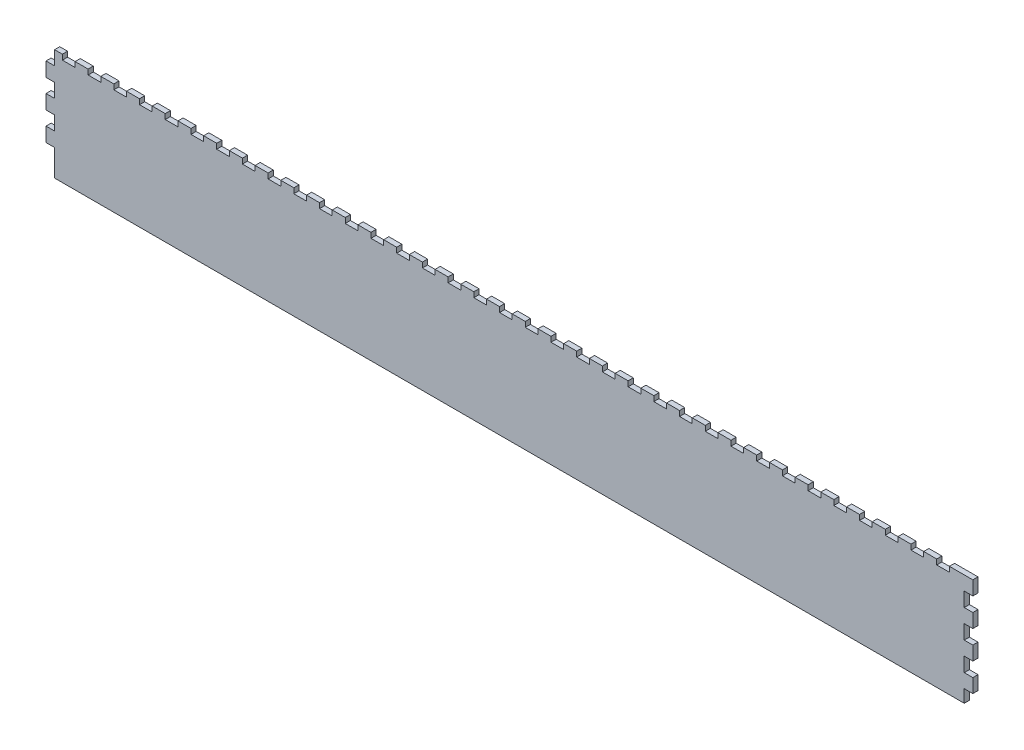
SolidWorks part; units mm, degrees
material "Perspex (TM) GS Acrylic Cast Sheet"
ref_plane "Front Plane" through (0, 0, 0) normal (0, 0, 1) x (1, 0, 0)
ref_plane "Top Plane" through (0, 0, 0) normal (0, 1, 0) x (1, 0, 0)
ref_plane "Right Plane" through (0, 0, 0) normal (1, 0, 0) x (0, 0, -1)
sketch "Sketch1" plane through (0, 0, 0) normal (0, 0, 1) x (1, 0, 0)
  line L0 (4.9997, 15.394) -> (4.9997, 0)
  line L1158 (538.3599, 64.6) -> (524.7414, 64.6)
  line L1159 (524.7414, 61.6) -> (524.7414, 64.6)
  line L1160 (524.7414, 61.6) -> (517.3729, 61.6)
  line L1161 (517.3729, 61.6) -> (517.3729, 64.6)
  line L1162 (517.3729, 64.6) -> (509.8045, 64.6)
  line L1163 (509.8045, 61.6) -> (509.8045, 64.6)
  line L1164 (509.8045, 61.6) -> (502.436, 61.6)
  line L1165 (502.436, 61.6) -> (502.436, 64.6)
  line L1166 (502.436, 64.6) -> (494.8676, 64.6)
  line L1167 (494.8676, 61.6) -> (494.8676, 64.6)
  line L1168 (494.8676, 61.6) -> (487.4991, 61.6)
  line L1169 (487.4991, 61.6) -> (487.4991, 64.6)
  line L1170 (487.4991, 64.6) -> (479.9307, 64.6)
  line L1171 (479.9307, 61.6) -> (479.9307, 64.6)
  line L1172 (479.9307, 61.6) -> (472.5622, 61.6)
  line L1173 (472.5622, 61.6) -> (472.5622, 64.6)
  line L1174 (472.5622, 64.6) -> (464.9938, 64.6)
  line L1175 (464.9938, 61.6) -> (464.9938, 64.6)
  line L1176 (464.9938, 61.6) -> (457.6253, 61.6)
  line L1177 (457.6253, 61.6) -> (457.6253, 64.6)
  line L1178 (457.6253, 64.6) -> (450.0567, 64.6)
  line L1179 (450.0567, 61.6) -> (450.0567, 64.6)
  line L1180 (450.0567, 61.6) -> (442.6886, 61.6)
  line L1181 (442.6886, 61.6) -> (442.6886, 64.6)
  line L1182 (442.6886, 64.6) -> (435.1201, 64.6)
  line L1183 (435.1201, 61.6) -> (435.1201, 64.6)
  line L1184 (435.1201, 61.6) -> (427.7516, 61.6)
  line L1185 (427.7516, 61.6) -> (427.7516, 64.6)
  line L1186 (427.7516, 64.6) -> (420.1831, 64.6)
  line L1187 (420.1831, 61.6) -> (420.1831, 64.6)
  line L1188 (420.1831, 61.6) -> (412.8147, 61.6)
  line L1189 (412.8147, 61.6) -> (412.8147, 64.6)
  line L1190 (412.8147, 64.6) -> (405.2462, 64.6)
  line L1191 (405.2462, 61.6) -> (405.2462, 64.6)
  line L1192 (405.2462, 61.6) -> (397.8777, 61.6)
  line L1193 (397.8777, 61.6) -> (397.8777, 64.6)
  line L1194 (397.8777, 64.6) -> (390.3092, 64.6)
  line L1195 (390.3092, 61.6) -> (390.3092, 64.6)
  line L1196 (390.3092, 61.6) -> (382.9407, 61.6)
  line L1197 (382.9407, 61.6) -> (382.9407, 64.6)
  line L1198 (382.9407, 64.6) -> (375.3722, 64.6)
  line L1199 (375.3722, 61.6) -> (375.3722, 64.6)
  line L1200 (375.3722, 61.6) -> (368.0038, 61.6)
  line L1201 (368.0038, 61.6) -> (368.0038, 64.6)
  line L1202 (368.0038, 64.6) -> (360.4356, 64.6)
  line L1203 (360.4356, 61.6) -> (360.4356, 64.6)
  line L1204 (360.4356, 61.6) -> (353.0672, 61.6)
  line L1205 (353.0672, 61.6) -> (353.0672, 64.6)
  line L1206 (353.0672, 64.6) -> (345.4986, 64.6)
  line L1207 (345.4986, 61.6) -> (345.4986, 64.6)
  line L1208 (345.4986, 61.6) -> (338.1302, 61.6)
  line L1209 (338.1302, 61.6) -> (338.1302, 64.6)
  line L1210 (338.1302, 64.6) -> (330.5617, 64.6)
  line L1211 (330.5617, 61.6) -> (330.5617, 64.6)
  line L1212 (330.5617, 61.6) -> (323.1932, 61.6)
  line L1213 (323.1932, 61.6) -> (323.1932, 64.6)
  line L1214 (323.1932, 64.6) -> (315.6247, 64.6)
  line L1215 (315.6247, 61.6) -> (315.6247, 64.6)
  line L1216 (315.6247, 61.6) -> (308.2563, 61.6)
  line L1217 (308.2563, 61.6) -> (308.2563, 64.6)
  line L1218 (308.2563, 64.6) -> (300.6878, 64.6)
  line L1219 (300.6878, 61.6) -> (300.6878, 64.6)
  line L1220 (300.6878, 61.6) -> (293.3193, 61.6)
  line L1221 (293.3193, 61.6) -> (293.3193, 64.6)
  line L1222 (293.3193, 64.6) -> (285.7508, 64.6)
  line L1223 (285.7508, 61.6) -> (285.7508, 64.6)
  line L1224 (285.7508, 61.6) -> (278.3823, 61.6)
  line L1225 (278.3823, 61.6) -> (278.3823, 64.6)
  line L1226 (278.3823, 64.6) -> (270.8142, 64.6)
  line L1227 (270.8142, 61.6) -> (270.8142, 64.6)
  line L1228 (270.8142, 61.6) -> (263.4457, 61.6)
  line L1229 (263.4457, 61.6) -> (263.4457, 64.6)
  line L1230 (263.4457, 64.6) -> (255.8772, 64.6)
  line L1231 (255.8772, 61.6) -> (255.8772, 64.6)
  line L1232 (255.8772, 61.6) -> (248.5088, 61.6)
  line L1233 (248.5088, 61.6) -> (248.5087, 64.6)
  line L1234 (248.5087, 64.6) -> (240.9403, 64.6)
  line L1235 (240.9403, 61.6) -> (240.9403, 64.6)
  line L1236 (240.9403, 61.6) -> (233.5718, 61.6)
  line L1237 (233.5718, 61.6) -> (233.5718, 64.6)
  line L1238 (233.5718, 64.6) -> (226.0033, 64.6)
  line L1239 (226.0033, 61.6) -> (226.0033, 64.6)
  line L1240 (226.0033, 61.6) -> (218.6348, 61.6)
  line L1241 (218.6348, 61.6) -> (218.6348, 64.6)
  line L1242 (218.6348, 64.6) -> (211.0664, 64.6)
  line L1243 (211.0664, 61.6) -> (211.0664, 64.6)
  line L1244 (211.0664, 61.6) -> (203.6979, 61.6)
  line L1245 (203.6979, 61.6) -> (203.6979, 64.6)
  line L1246 (203.6979, 64.6) -> (196.1297, 64.6)
  line L1247 (196.1297, 61.6) -> (196.1297, 64.6)
  line L1248 (196.1297, 61.6) -> (188.7613, 61.6)
  line L1249 (188.7613, 61.6) -> (188.7613, 64.6)
  line L1250 (188.7613, 64.6) -> (181.1928, 64.6)
  line L1251 (181.1928, 61.6) -> (181.1928, 64.6)
  line L1252 (181.1928, 61.6) -> (173.8243, 61.6)
  line L1253 (173.8243, 61.6) -> (173.8243, 64.6)
  line L1254 (173.8243, 64.6) -> (166.2558, 64.6)
  line L1255 (166.2558, 61.6) -> (166.2558, 64.6)
  line L1256 (166.2558, 61.6) -> (158.8873, 61.6)
  line L1257 (158.8873, 61.6) -> (158.8873, 64.6)
  line L1258 (158.8873, 64.6) -> (151.3188, 64.6)
  line L1259 (151.3188, 61.6) -> (151.3188, 64.6)
  line L1260 (151.3188, 61.6) -> (143.9504, 61.6)
  line L1261 (143.9504, 61.6) -> (143.9504, 64.6)
  line L1262 (143.9504, 64.6) -> (136.3819, 64.6)
  line L1263 (136.3819, 61.6) -> (136.3819, 64.6)
  line L1264 (136.3819, 61.6) -> (129.0134, 61.6)
  line L1265 (129.0134, 61.6) -> (129.0134, 64.6)
  line L1266 (129.0134, 64.6) -> (121.4449, 64.6)
  line L1267 (121.4449, 61.6) -> (121.4449, 64.6)
  line L1268 (121.4449, 61.6) -> (114.0764, 61.6)
  line L1269 (114.0764, 61.6) -> (114.0764, 64.6)
  line L1270 (114.0764, 64.6) -> (106.5083, 64.6)
  line L1271 (106.5083, 61.6) -> (106.5083, 64.6)
  line L1272 (106.5083, 61.6) -> (99.1398, 61.6)
  line L1273 (99.1398, 61.6) -> (99.1398, 64.6)
  line L1274 (99.1398, 64.6) -> (91.5713, 64.6)
  line L1275 (91.5713, 61.6) -> (91.5713, 64.6)
  line L1276 (91.5713, 61.6) -> (84.2029, 61.6)
  line L1277 (84.2029, 61.6) -> (84.2029, 64.6)
  line L1278 (84.2029, 64.6) -> (76.6344, 64.6)
  line L1279 (76.6344, 61.6) -> (76.6344, 64.6)
  line L1280 (76.6344, 61.6) -> (69.2659, 61.6)
  line L1281 (69.2659, 61.6) -> (69.2659, 64.6)
  line L1282 (69.2659, 64.6) -> (61.6974, 64.6)
  line L1283 (61.6974, 61.6) -> (61.6974, 64.6)
  line L1284 (61.6974, 61.6) -> (54.3289, 61.6)
  line L1285 (54.3289, 61.6) -> (54.3289, 64.6)
  line L1286 (54.3289, 64.6) -> (46.7604, 64.6)
  line L1287 (46.7604, 61.6) -> (46.7604, 64.6)
  line L1288 (46.7604, 61.6) -> (39.392, 61.6)
  line L1289 (39.392, 61.6) -> (39.392, 64.6)
  line L1290 (39.392, 64.6) -> (31.8235, 64.6)
  line L1291 (31.8235, 61.6) -> (31.8235, 64.6)
  line L1292 (31.8235, 61.6) -> (24.4554, 61.6)
  line L1293 (24.4554, 61.6) -> (24.4554, 64.6)
  line L1294 (24.4554, 64.6) -> (16.8869, 64.6)
  line L1295 (16.8869, 61.6) -> (16.8869, 64.6)
  line L1296 (16.8869, 61.6) -> (9.5184, 61.6)
  line L1297 (9.5184, 61.6) -> (9.5184, 64.6)
  line L1298 (9.5184, 64.6) -> (4.9997, 64.6)
  line L1299 (538.3599, 64.6) -> (538.3599, 56.4542)
  line L1300 (533.3598, 56.4542) -> (538.3599, 56.4542)
  line L1301 (533.3598, 56.4542) -> (533.3598, 48.1649)
  line L1302 (533.3598, 48.1649) -> (538.3599, 48.1649)
  line L1303 (538.3599, 48.1649) -> (538.3599, 40.0757)
  line L1304 (533.3598, 40.0757) -> (538.3599, 40.0757)
  line L1305 (533.3598, 40.0757) -> (533.3598, 31.7864)
  line L1306 (533.3598, 31.7864) -> (538.3599, 31.7864)
  line L1307 (538.3599, 31.7864) -> (538.3599, 23.7267)
  line L1308 (4.9997, 64.6) -> (4.9997, 56.4542)
  line L1309 (0, 56.4542) -> (4.9997, 56.4542)
  line L1310 (0, 56.4542) -> (0, 48.1649)
  line L1311 (0, 48.1649) -> (4.9997, 48.1649)
  line L1312 (4.9997, 48.1649) -> (4.9997, 40.0757)
  line L1313 (0, 40.0757) -> (4.9997, 40.0757)
  line L1314 (0, 40.0757) -> (0, 31.7864)
  line L1315 (0, 31.7864) -> (4.9997, 31.7864)
  line L1316 (4.9997, 31.7864) -> (4.9997, 23.6833)
  line L1317 (4.9997, 0) -> (533.3598, 0)
  line L1318 (533.3598, 23.7267) -> (538.3599, 23.7267)
  line L1319 (533.3598, 23.7267) -> (533.3598, 15.4209)
  line L1320 (533.3598, 15.4209) -> (538.3599, 15.4209)
  line L1321 (538.3599, 15.4209) -> (538.3599, 7.3612)
  line L1322 (533.3598, 7.3612) -> (538.3599, 7.3612)
  line L1323 (533.3598, 7.3612) -> (533.3598, 0)
  line L1324 (0, 23.6833) -> (4.9997, 23.6833)
  line L1325 (0, 23.6833) -> (0, 15.394)
  line L1326 (0, 15.394) -> (4.9997, 15.394)
extrude "Boss-Extrude1" add sketch "Sketch1" along normal blind 3
sketch "Sketch3" plane through (0, 0, 3) normal (0, 0, 1) x (1, 0, 0)
  line L0 (388.1696, 22.6554) -> (388.1696, 19.4364)
  line L1 (390.0144, 23.5966) -> (388.1696, 22.6554)
  line L2 (391.8592, 24.5377) -> (390.0144, 23.5966)
  line L3 (391.8592, 20.3776) -> (391.8592, 24.5377)
  line L4 (391.8592, 16.2174) -> (391.8592, 20.3776)
  line L5 (390.0144, 16.2174) -> (391.8592, 16.2174)
  line L6 (388.1696, 16.2174) -> (390.0144, 16.2174)
  line L7 (388.1696, 19.4364) -> (388.1696, 16.2174)
  line L8 (393.704, 27.2964) -> (393.704, 20.8345)
  line L9 (390.0144, 25.4413) -> (393.704, 27.2964)
  line L10 (386.3248, 23.5862) -> (390.0144, 25.4413)
  line L11 (386.3248, 18.9794) -> (386.3248, 23.5862)
  line L12 (386.3248, 14.3726) -> (386.3248, 18.9794)
  line L13 (390.0144, 14.3726) -> (386.3248, 14.3726)
  line L14 (393.704, 14.3726) -> (390.0144, 14.3726)
  line L15 (393.704, 20.8345) -> (393.704, 14.3726)
  line L16 (434.7504, 28.1897) -> (434.7504, 22.2036)
  line L17 (436.5952, 29.1309) -> (434.7504, 28.1897)
  line L18 (438.44, 30.072) -> (436.5952, 29.1309)
  line L19 (438.44, 23.1447) -> (438.44, 30.072)
  line L20 (438.44, 16.2174) -> (438.44, 23.1447)
  line L21 (436.5952, 16.2174) -> (438.44, 16.2174)
  line L22 (434.7504, 16.2174) -> (436.5952, 16.2174)
  line L23 (434.7504, 22.2036) -> (434.7504, 16.2174)
  line L24 (432.9056, 29.0475) -> (436.3429, 30.934)
  line L25 (432.9056, 21.7101) -> (432.9056, 29.0475)
  line L26 (432.9056, 14.3726) -> (432.9056, 21.7101)
  line L27 (436.5952, 14.3726) -> (432.9056, 14.3726)
  line L28 (440.2848, 14.3726) -> (436.5952, 14.3726)
  line L29 (440.2848, 23.5966) -> (440.2848, 14.3726)
  line L30 (146.503, 36.9712) -> (146.503, 26.5943)
  line L31 (148.3478, 36.9712) -> (146.503, 36.9712)
  line L32 (150.1926, 36.9712) -> (148.3478, 36.9712)
  line L33 (150.1926, 26.5943) -> (150.1926, 36.9712)
  line L34 (150.1926, 16.2174) -> (150.1926, 26.5943)
  line L35 (148.3478, 16.2174) -> (150.1926, 16.2174)
  line L36 (146.503, 16.2174) -> (148.3478, 16.2174)
  line L37 (146.503, 26.5943) -> (146.503, 16.2174)
  line L38 (152.0374, 38.816) -> (152.0374, 26.5943)
  line L39 (148.3478, 38.816) -> (152.0374, 38.816)
  line L40 (144.6582, 38.816) -> (148.3478, 38.816)
  line L41 (144.6582, 26.5943) -> (144.6582, 38.816)
  line L42 (144.6582, 14.3726) -> (144.6582, 26.5943)
  line L43 (148.3478, 14.3726) -> (144.6582, 14.3726)
  line L44 (152.0374, 14.3726) -> (148.3478, 14.3726)
  line L45 (152.0374, 26.5943) -> (152.0374, 14.3726)
  line L46 (186.6271, 36.9712) -> (186.6271, 26.5943)
  line L47 (188.4718, 36.9712) -> (186.6271, 36.9712)
  line L48 (190.3166, 36.9712) -> (188.4718, 36.9712)
  line L49 (190.3166, 26.5943) -> (190.3166, 36.9712)
  line L50 (190.3166, 16.2174) -> (190.3166, 26.5943)
  line L51 (188.4718, 16.2174) -> (190.3166, 16.2174)
  line L52 (186.6271, 16.2174) -> (188.4718, 16.2174)
  line L53 (186.6271, 26.5943) -> (186.6271, 16.2174)
  line L54 (192.1614, 38.816) -> (192.1614, 26.5943)
  line L55 (188.4718, 38.816) -> (192.1614, 38.816)
  line L56 (184.7823, 38.816) -> (188.4718, 38.816)
  line L57 (184.7823, 26.5943) -> (184.7823, 38.816)
  line L58 (184.7823, 14.3726) -> (184.7823, 26.5943)
  line L59 (188.4718, 14.3726) -> (184.7823, 14.3726)
  line L60 (192.1614, 14.3726) -> (188.4718, 14.3726)
  line L61 (192.1614, 26.5943) -> (192.1614, 14.3726)
  line L62 (393.704, 38.816) -> (393.704, 35.1213)
  line L63 (390.0144, 38.816) -> (393.704, 38.816)
  line L64 (386.3248, 38.816) -> (390.0144, 38.816)
  line L65 (386.3248, 36.9764) -> (386.3248, 38.816)
  line L66 (393.704, 31.4266) -> (390.0144, 33.2817)
  line L67 (393.704, 35.1213) -> (393.704, 31.4266)
  line L68 (307.6212, 47.3012) -> (307.6214, 47.3012)
  line L69 (305.9931, 14.3726) -> (306.1502, 32.1059)
  line L70 (308.802, 14.3726) -> (305.9931, 14.3726)
  line L71 (311.611, 14.3726) -> (308.802, 14.3726)
  line L72 (311.611, 12.5279) -> (311.611, 14.3726)
  line L73 (311.611, 10.683) -> (311.611, 12.5279)
  line L74 (304.2319, 10.683) -> (311.611, 10.683)
  line L75 (296.8527, 10.683) -> (304.2319, 10.683)
  line L76 (296.8527, 12.5279) -> (296.8527, 10.683)
  line L77 (296.8527, 14.3726) -> (296.8527, 12.5279)
  line L78 (299.6653, 14.3726) -> (296.8527, 14.3726)
  line L79 (302.478, 14.3726) -> (299.6653, 14.3726)
  line L80 (302.3172, 32.1058) -> (302.478, 14.3726)
  line L81 (300.5424, 16.2174) -> (300.5455, 30.3992)
  line L82 (297.7752, 16.2174) -> (300.5424, 16.2174)
  line L83 (295.0081, 16.2174) -> (297.7752, 16.2174)
  line L84 (295.0081, 12.5279) -> (295.0081, 16.2174)
  line L85 (295.0081, 8.8383) -> (295.0081, 12.5279)
  line L86 (304.232, 8.8383) -> (295.0081, 8.8383)
  line L87 (313.4559, 8.8383) -> (304.232, 8.8383)
  line L88 (313.4559, 12.5279) -> (313.4559, 8.8383)
  line L89 (313.4559, 16.2174) -> (313.4559, 12.5279)
  line L90 (310.6887, 16.2174) -> (313.4559, 16.2174)
  line L91 (307.9215, 16.2174) -> (310.6887, 16.2174)
  line L92 (307.9215, 29.9837) -> (307.9215, 16.2174)
  line L93 (434.8264, 41.7178) -> (436.4182, 40.9587)
  line L94 (434.5024, 46.0388) -> (434.8264, 41.7178)
  line L95 (440.2848, 36.9084) -> (436.5956, 38.8999)
  line L96 (440.2848, 40.3292) -> (440.2848, 36.9084)
  line L97 (443.8891, 10.683) -> (444.0767, 29.938)
  line L98 (436.5526, 10.683) -> (443.8891, 10.683)
  line L99 (429.2161, 10.683) -> (436.5526, 10.683)
  line L100 (429.2161, 21.1916) -> (429.2161, 10.683)
  line L101 (429.2161, 31.7001) -> (429.2161, 21.1916)
  line L102 (432.2682, 33.2052) -> (429.2161, 31.7001)
  line L103 (429.4466, 38.1242) -> (432.0696, 36.7311)
  line L104 (429.108, 43.1974) -> (429.4466, 38.1242)
  line L105 (427.3713, 37.155) -> (427.4169, 41.7904)
  line L106 (429.5604, 36.0915) -> (427.3713, 37.155)
  line L107 (431.7495, 35.0279) -> (429.5604, 36.0915)
  line L108 (429.5604, 33.9153) -> (431.7495, 35.0279)
  line L109 (427.3713, 32.8028) -> (429.5604, 33.9153)
  line L110 (427.3713, 20.8205) -> (427.3713, 32.8028)
  line L111 (427.3713, 8.8383) -> (427.3713, 20.8205)
  line L112 (436.5952, 8.8383) -> (427.3713, 8.8383)
  line L113 (445.8191, 8.8383) -> (436.5952, 8.8383)
  line L115 (445.8191, 26.5247) -> (445.8191, 8.8383)
  line L116 (209.3814, 48.2705) -> (209.3813, 48.2705)
  line L117 (213.607, 33.0511) -> (213.8934, 39.969)
  line L118 (211.6626, 38.816) -> (213.607, 33.0511)
  line L119 (226.29, 8.8383) -> (226.3356, 28.0932)
  line L120 (229.9795, 8.8383) -> (226.29, 8.8383)
  line L121 (233.6691, 8.8383) -> (229.9795, 8.8383)
  line L122 (233.6691, 20.1376) -> (233.6691, 8.8383)
  line L123 (233.6691, 31.4369) -> (233.6691, 20.1376)
  line L124 (235.5139, 31.4369) -> (233.6691, 31.4369)
  line L125 (237.3587, 31.4369) -> (235.5139, 31.4369)
  line L126 (237.3587, 20.1376) -> (237.3587, 31.4369)
  line L127 (237.3587, 8.8383) -> (237.3587, 20.1376)
  line L128 (241.0482, 8.8383) -> (237.3587, 8.8383)
  line L129 (244.7378, 8.8383) -> (241.0482, 8.8383)
  line L130 (244.735, 26.2484) -> (244.7378, 8.8383)
  line L131 (242.814, 10.683) -> (243.0138, 29.7074)
  line L132 (241.0087, 10.683) -> (242.814, 10.683)
  line L133 (239.2034, 10.683) -> (241.0087, 10.683)
  line L134 (239.2034, 21.9824) -> (239.2034, 10.683)
  line L135 (239.2034, 33.2817) -> (239.2034, 21.9824)
  line L136 (235.5138, 33.2817) -> (239.2034, 33.2817)
  line L137 (231.8242, 33.2817) -> (235.5138, 33.2817)
  line L138 (231.8242, 21.9824) -> (231.8242, 33.2817)
  line L139 (231.8242, 10.683) -> (231.8242, 21.9824)
  line L140 (230.0246, 10.683) -> (231.8242, 10.683)
  line L141 (228.225, 10.683) -> (230.0246, 10.683)
  line L142 (228.0101, 30.3992) -> (228.225, 10.683)
  line L143 (115.6029, 25.9025) -> (115.6485, 37.5477)
  line L144 (119.2925, 25.9025) -> (115.6029, 25.9025)
  line L145 (122.982, 25.9025) -> (119.2925, 25.9025)
  line L146 (122.982, 31.4369) -> (122.982, 25.9025)
  line L147 (122.982, 36.9712) -> (122.982, 31.4369)
  line L148 (124.8268, 36.9712) -> (122.982, 36.9712)
  line L149 (126.6716, 36.9712) -> (124.8268, 36.9712)
  line L150 (126.6716, 26.5943) -> (126.6716, 36.9712)
  line L151 (126.6716, 16.2174) -> (126.6716, 26.5943)
  line L152 (124.8268, 16.2174) -> (126.6716, 16.2174)
  line L153 (122.982, 16.2174) -> (124.8268, 16.2174)
  line L154 (122.982, 18.9846) -> (122.982, 16.2174)
  line L155 (122.982, 21.7517) -> (122.982, 18.9846)
  line L156 (119.2925, 21.7517) -> (122.982, 21.7517)
  line L157 (115.6029, 21.7517) -> (119.2925, 21.7517)
  line L158 (115.6029, 15.295) -> (115.6029, 21.7517)
  line L159 (115.6029, 8.8383) -> (115.6029, 15.295)
  line L160 (124.8268, 8.8383) -> (115.6029, 8.8383)
  line L161 (134.0507, 8.8383) -> (124.8268, 8.8383)
  line L162 (134.0507, 26.0635) -> (134.0507, 8.8383)
  line L163 (132.1262, 10.683) -> (132.3074, 29.4768)
  line L164 (124.787, 10.683) -> (132.1262, 10.683)
  line L165 (117.4477, 10.683) -> (124.787, 10.683)
  line L166 (117.4477, 15.295) -> (117.4477, 10.683)
  line L167 (117.4477, 19.907) -> (117.4477, 15.295)
  line L168 (119.2925, 19.907) -> (117.4477, 19.907)
  line L169 (121.1373, 19.907) -> (119.2925, 19.907)
  line L170 (121.1373, 17.1398) -> (121.1373, 19.907)
  line L171 (121.1373, 14.3726) -> (121.1373, 17.1398)
  line L172 (124.8268, 14.3726) -> (121.1373, 14.3726)
  line L173 (128.5164, 14.3726) -> (124.8268, 14.3726)
  line L174 (128.5164, 26.5943) -> (128.5164, 14.3726)
  line L175 (128.5164, 38.816) -> (128.5164, 26.5943)
  line L176 (124.8268, 38.816) -> (128.5164, 38.816)
  line L177 (121.1373, 38.816) -> (124.8268, 38.816)
  line L178 (121.1373, 33.2817) -> (121.1373, 38.816)
  line L179 (121.1373, 27.7473) -> (121.1373, 33.2817)
  line L180 (119.3512, 27.7473) -> (121.1373, 27.7473)
  line L181 (117.565, 27.7473) -> (119.3512, 27.7473)
  line L182 (117.3014, 39.6231) -> (117.565, 27.7473)
  line L183 (173.8694, 51.0505) -> (173.8695, 51.0505)
  line L184 (172.2496, 10.683) -> (172.4314, 31.5522)
  line L185 (170.445, 10.683) -> (172.2496, 10.683)
  line L186 (168.6403, 10.683) -> (170.445, 10.683)
  line L187 (168.6403, 24.7495) -> (168.6403, 10.683)
  line L188 (168.6403, 38.816) -> (168.6403, 24.7495)
  line L189 (165.9388, 38.816) -> (168.6403, 38.816)
  line L190 (163.2372, 38.816) -> (165.9388, 38.816)
  line L191 (162.9119, 44.0045) -> (163.2372, 38.816)
  line L192 (161.2613, 36.9712) -> (161.2644, 40.3149)
  line L193 (164.0285, 36.9712) -> (161.2613, 36.9712)
  line L194 (166.7956, 36.9712) -> (164.0285, 36.9712)
  line L195 (166.7956, 22.9047) -> (166.7956, 36.9712)
  line L196 (166.7956, 8.8383) -> (166.7956, 22.9047)
  line L197 (170.4852, 8.8383) -> (166.7956, 8.8383)
  line L198 (174.1748, 8.8383) -> (170.4852, 8.8383)
  line L199 (174.1748, 28.1389) -> (174.1748, 8.8383)
  line L200 (249.3497, 31.4369) -> (249.3953, 40.5455)
  line L201 (253.0393, 31.4369) -> (249.3497, 31.4369)
  line L202 (256.7288, 31.4369) -> (253.0393, 31.4369)
  line L203 (256.7288, 34.204) -> (256.7288, 31.4369)
  line L204 (256.7288, 36.9712) -> (256.7288, 34.204)
  line L205 (258.5736, 36.9712) -> (256.7288, 36.9712)
  line L206 (260.4184, 36.9712) -> (258.5736, 36.9712)
  line L207 (260.4184, 26.5943) -> (260.4184, 36.9712)
  line L208 (260.4184, 16.2174) -> (260.4184, 26.5943)
  line L209 (258.5736, 16.2174) -> (260.4184, 16.2174)
  line L210 (256.7288, 16.2174) -> (258.5736, 16.2174)
  line L211 (256.7288, 18.9846) -> (256.7288, 16.2174)
  line L212 (256.7288, 21.7517) -> (256.7288, 18.9846)
  line L213 (253.0393, 21.7517) -> (256.7288, 21.7517)
  line L214 (249.3497, 21.7517) -> (253.0393, 21.7517)
  line L215 (249.3497, 15.295) -> (249.3497, 21.7517)
  line L216 (249.3497, 8.8383) -> (249.3497, 15.295)
  line L217 (258.5736, 8.8383) -> (249.3497, 8.8383)
  line L218 (267.7975, 8.8383) -> (258.5736, 8.8383)
  line L219 (267.7975, 26.2941) -> (267.7975, 8.8383)
  line L220 (265.8667, 10.683) -> (266.0553, 29.7074)
  line L221 (258.5306, 10.683) -> (265.8667, 10.683)
  line L222 (251.1945, 10.683) -> (258.5306, 10.683)
  line L223 (251.1945, 15.295) -> (251.1945, 10.683)
  line L224 (251.1945, 19.907) -> (251.1945, 15.295)
  line L225 (253.0393, 19.907) -> (251.1945, 19.907)
  line L226 (254.884, 19.907) -> (253.0393, 19.907)
  line L227 (254.884, 17.1398) -> (254.884, 19.907)
  line L228 (254.884, 14.3726) -> (254.884, 17.1398)
  line L229 (258.5736, 14.3726) -> (254.884, 14.3726)
  line L230 (262.2632, 14.3726) -> (258.5736, 14.3726)
  line L231 (262.2632, 26.5943) -> (262.2632, 14.3726)
  line L232 (262.2632, 38.816) -> (262.2632, 26.5943)
  line L233 (258.5736, 38.816) -> (262.2632, 38.816)
  line L234 (254.884, 38.816) -> (258.5736, 38.816)
  line L235 (254.884, 36.0488) -> (254.884, 38.816)
  line L236 (254.884, 33.2817) -> (254.884, 36.0488)
  line L237 (253.1053, 33.2817) -> (254.884, 33.2817)
  line L238 (251.3265, 33.2817) -> (253.1053, 33.2817)
  line L239 (251.0415, 42.6209) -> (251.3265, 33.2817)
  line L240 (352.3522, 51.0505) -> (352.3523, 51.0505)
  line L241 (350.7324, 10.683) -> (350.9142, 31.5522)
  line L242 (348.9277, 10.683) -> (350.7324, 10.683)
  line L243 (347.1231, 10.683) -> (348.9277, 10.683)
  line L244 (347.1231, 24.7495) -> (347.1231, 10.683)
  line L245 (347.1231, 38.816) -> (347.1231, 24.7495)
  line L246 (344.4215, 38.816) -> (347.1231, 38.816)
  line L247 (341.72, 38.816) -> (344.4215, 38.816)
  line L248 (341.3947, 44.0045) -> (341.72, 38.816)
  line L249 (339.7441, 36.9712) -> (339.7472, 40.3149)
  line L250 (342.5112, 36.9712) -> (339.7441, 36.9712)
  line L251 (345.2784, 36.9712) -> (342.5112, 36.9712)
  line L252 (345.2784, 22.9047) -> (345.2784, 36.9712)
  line L253 (345.2784, 8.8383) -> (345.2784, 22.9047)
  line L254 (348.968, 8.8383) -> (345.2784, 8.8383)
  line L255 (352.6576, 8.8383) -> (348.968, 8.8383)
  line L256 (352.6576, 28.1389) -> (352.6576, 8.8383)
  line L257 (397.3133, 10.683) -> (397.4951, 31.5522)
  line L258 (389.9743, 10.683) -> (397.3133, 10.683)
  line L259 (382.6353, 10.683) -> (389.9743, 10.683)
  line L260 (382.6353, 18.4244) -> (382.6353, 10.683)
  line L261 (382.6353, 26.1657) -> (382.6353, 18.4244)
  line L262 (385.6874, 27.6708) -> (382.6353, 26.1657)
  line L263 (382.8659, 32.5898) -> (385.4889, 31.1967)
  line L264 (382.5801, 40.208) -> (382.8659, 32.5898)
  line L265 (380.7905, 31.6207) -> (380.8361, 38.7926)
  line L266 (382.9665, 30.5635) -> (380.7905, 31.6207)
  line L267 (385.1425, 29.5063) -> (382.9665, 30.5635)
  line L268 (383.3124, 28.3986) -> (385.1425, 29.5063)
  line L269 (380.7905, 8.8383) -> (380.7905, 18.0622)
  line L270 (390.0144, 8.8383) -> (380.7905, 8.8383)
  line L271 (399.2383, 8.8383) -> (390.0144, 8.8383)
  line L272 (399.2383, 28.1389) -> (399.2383, 8.8383)
  line L273 (272.4095, 36.9712) -> (272.4551, 43.5433)
  line L274 (277.9438, 36.9712) -> (272.4095, 36.9712)
  line L275 (283.4782, 36.9712) -> (277.9438, 36.9712)
  line L276 (283.4782, 35.1264) -> (283.4782, 36.9712)
  line L277 (283.4782, 33.2817) -> (283.4782, 35.1264)
  line L278 (277.9438, 33.2817) -> (283.4782, 33.2817)
  line L279 (272.4095, 33.2817) -> (277.9438, 33.2817)
  line L280 (272.4095, 29.5921) -> (272.4095, 33.2817)
  line L281 (272.4095, 25.9025) -> (272.4095, 29.5921)
  line L282 (277.9438, 25.9025) -> (272.4095, 25.9025)
  line L283 (283.4782, 25.9025) -> (277.9438, 25.9025)
  line L284 (283.4782, 21.06) -> (283.4782, 25.9025)
  line L285 (283.4782, 16.2174) -> (283.4782, 21.06)
  line L286 (281.6334, 16.2174) -> (283.4782, 16.2174)
  line L287 (279.7886, 16.2174) -> (281.6334, 16.2174)
  line L288 (279.7886, 18.9846) -> (279.7886, 16.2174)
  line L289 (279.7886, 21.7517) -> (279.7886, 18.9846)
  line L290 (276.099, 21.7517) -> (279.7886, 21.7517)
  line L291 (272.4095, 21.7517) -> (276.099, 21.7517)
  line L292 (272.4095, 15.295) -> (272.4095, 21.7517)
  line L293 (272.4095, 8.8383) -> (272.4095, 15.295)
  line L294 (281.6334, 8.8383) -> (272.4095, 8.8383)
  line L295 (290.8573, 8.8383) -> (281.6334, 8.8383)
  line L296 (290.8573, 26.9859) -> (290.8573, 8.8383)
  line L297 (288.9288, 10.683) -> (289.1147, 30.3992)
  line L298 (281.5915, 10.683) -> (288.9288, 10.683)
  line L299 (274.2543, 10.683) -> (281.5915, 10.683)
  line L300 (274.2543, 15.295) -> (274.2543, 10.683)
  line L301 (274.2543, 19.907) -> (274.2543, 15.295)
  line L302 (276.099, 19.907) -> (274.2543, 19.907)
  line L303 (277.9438, 19.907) -> (276.099, 19.907)
  line L304 (277.9438, 17.1398) -> (277.9438, 19.907)
  line L305 (277.9438, 14.3726) -> (277.9438, 17.1398)
  line L306 (281.6334, 14.3726) -> (277.9438, 14.3726)
  line L307 (285.323, 14.3726) -> (281.6334, 14.3726)
  line L308 (285.323, 21.06) -> (285.323, 14.3726)
  line L309 (285.323, 27.7473) -> (285.323, 21.06)
  line L310 (279.7886, 27.7473) -> (285.323, 27.7473)
  line L311 (274.2543, 27.7473) -> (279.7886, 27.7473)
  line L312 (274.2543, 29.5921) -> (274.2543, 27.7473)
  line L313 (274.2543, 31.4369) -> (274.2543, 29.5921)
  line L314 (279.7886, 31.4369) -> (274.2543, 31.4369)
  line L315 (285.323, 31.4369) -> (279.7886, 31.4369)
  line L316 (285.323, 35.1264) -> (285.323, 31.4369)
  line L317 (285.323, 38.816) -> (285.323, 35.1264)
  line L318 (279.8603, 38.816) -> (285.323, 38.816)
  line L319 (274.3977, 38.816) -> (279.8603, 38.816)
  line L320 (274.0865, 45.6186) -> (274.3977, 38.816)
  line L321 (357.2695, 36.9712) -> (357.3151, 43.5433)
  line L322 (362.8039, 36.9712) -> (357.2695, 36.9712)
  line L323 (368.3382, 36.9712) -> (362.8039, 36.9712)
  line L324 (368.3382, 35.1264) -> (368.3382, 36.9712)
  line L325 (368.3382, 33.2817) -> (368.3382, 35.1264)
  line L326 (362.8039, 33.2817) -> (368.3382, 33.2817)
  line L327 (357.2695, 33.2817) -> (362.8039, 33.2817)
  line L328 (357.2695, 29.5921) -> (357.2695, 33.2817)
  line L329 (357.2695, 25.9025) -> (357.2695, 29.5921)
  line L330 (362.8039, 25.9025) -> (357.2695, 25.9025)
  line L331 (368.3382, 25.9025) -> (362.8039, 25.9025)
  line L332 (368.3382, 21.06) -> (368.3382, 25.9025)
  line L333 (368.3382, 16.2174) -> (368.3382, 21.06)
  line L334 (366.4934, 16.2174) -> (368.3382, 16.2174)
  line L335 (364.6486, 16.2174) -> (366.4934, 16.2174)
  line L336 (364.6486, 18.9846) -> (364.6486, 16.2174)
  line L337 (364.6486, 21.7517) -> (364.6486, 18.9846)
  line L338 (360.9591, 21.7517) -> (364.6486, 21.7517)
  line L339 (357.2695, 21.7517) -> (360.9591, 21.7517)
  line L340 (357.2695, 15.295) -> (357.2695, 21.7517)
  line L341 (357.2695, 8.8383) -> (357.2695, 15.295)
  line L342 (366.4934, 8.8383) -> (357.2695, 8.8383)
  line L343 (375.7173, 8.8383) -> (366.4934, 8.8383)
  line L344 (375.7173, 26.9859) -> (375.7173, 8.8383)
  line L345 (373.7888, 10.683) -> (373.9747, 30.3992)
  line L346 (366.4515, 10.683) -> (373.7888, 10.683)
  line L347 (359.1143, 10.683) -> (366.4515, 10.683)
  line L348 (359.1143, 15.295) -> (359.1143, 10.683)
  line L349 (359.1143, 19.907) -> (359.1143, 15.295)
  line L350 (360.9591, 19.907) -> (359.1143, 19.907)
  line L351 (362.8039, 19.907) -> (360.9591, 19.907)
  line L352 (362.8039, 17.1398) -> (362.8039, 19.907)
  line L353 (362.8039, 14.3726) -> (362.8039, 17.1398)
  line L354 (366.4934, 14.3726) -> (362.8039, 14.3726)
  line L355 (370.183, 14.3726) -> (366.4934, 14.3726)
  line L356 (370.183, 21.06) -> (370.183, 14.3726)
  line L357 (370.183, 27.7473) -> (370.183, 21.06)
  line L358 (364.6486, 27.7473) -> (370.183, 27.7473)
  line L359 (359.1143, 27.7473) -> (364.6486, 27.7473)
  line L360 (359.1143, 29.5921) -> (359.1143, 27.7473)
  line L361 (359.1143, 31.4369) -> (359.1143, 29.5921)
  line L362 (364.6486, 31.4369) -> (359.1143, 31.4369)
  line L363 (370.183, 31.4369) -> (364.6486, 31.4369)
  line L364 (370.183, 35.1264) -> (370.183, 31.4369)
  line L365 (370.183, 38.816) -> (370.183, 35.1264)
  line L366 (364.7204, 38.816) -> (370.183, 38.816)
  line L367 (359.2577, 38.816) -> (364.7204, 38.816)
  line L368 (358.9465, 45.6186) -> (359.2577, 38.816)
  line L369 (403.8503, 36.9712) -> (403.8959, 43.5433)
  line L370 (409.3846, 36.9712) -> (403.8503, 36.9712)
  line L371 (414.919, 36.9712) -> (409.3846, 36.9712)
  line L372 (414.919, 35.1264) -> (414.919, 36.9712)
  line L373 (414.919, 33.2817) -> (414.919, 35.1264)
  line L374 (409.3846, 33.2817) -> (414.919, 33.2817)
  line L375 (403.8503, 33.2817) -> (409.3846, 33.2817)
  line L376 (403.8503, 29.5921) -> (403.8503, 33.2817)
  line L377 (403.8503, 25.9025) -> (403.8503, 29.5921)
  line L378 (409.3846, 25.9025) -> (403.8503, 25.9025)
  line L379 (414.919, 25.9025) -> (409.3846, 25.9025)
  line L380 (414.919, 21.06) -> (414.919, 25.9025)
  line L381 (414.919, 16.2174) -> (414.919, 21.06)
  line L382 (413.0742, 16.2174) -> (414.919, 16.2174)
  line L383 (411.2294, 16.2174) -> (413.0742, 16.2174)
  line L384 (411.2294, 18.9846) -> (411.2294, 16.2174)
  line L385 (411.2294, 21.7517) -> (411.2294, 18.9846)
  line L386 (407.5398, 21.7517) -> (411.2294, 21.7517)
  line L387 (403.8503, 21.7517) -> (407.5398, 21.7517)
  line L388 (403.8503, 15.295) -> (403.8503, 21.7517)
  line L389 (403.8503, 8.8383) -> (403.8503, 15.295)
  line L390 (413.0742, 8.8383) -> (403.8503, 8.8383)
  line L391 (422.2981, 8.8383) -> (413.0742, 8.8383)
  line L393 (422.2981, 26.9859) -> (422.2981, 8.8383)
  line L394 (420.3695, 10.683) -> (420.5554, 30.3992)
  line L395 (413.0323, 10.683) -> (420.3695, 10.683)
  line L396 (405.6951, 10.683) -> (413.0323, 10.683)
  line L397 (405.6951, 15.295) -> (405.6951, 10.683)
  line L398 (405.6951, 19.907) -> (405.6951, 15.295)
  line L399 (407.5398, 19.907) -> (405.6951, 19.907)
  line L400 (409.3846, 19.907) -> (407.5398, 19.907)
  line L401 (409.3846, 17.1398) -> (409.3846, 19.907)
  line L402 (409.3846, 14.3726) -> (409.3846, 17.1398)
  line L403 (413.0742, 14.3726) -> (409.3846, 14.3726)
  line L404 (416.7638, 14.3726) -> (413.0742, 14.3726)
  line L405 (416.7638, 21.06) -> (416.7638, 14.3726)
  line L406 (416.7638, 27.7473) -> (416.7638, 21.06)
  line L407 (411.2294, 27.7473) -> (416.7638, 27.7473)
  line L408 (405.6951, 27.7473) -> (411.2294, 27.7473)
  line L409 (405.6951, 29.5921) -> (405.6951, 27.7473)
  line L410 (405.6951, 31.4369) -> (405.6951, 29.5921)
  line L411 (411.2294, 31.4369) -> (405.6951, 31.4369)
  line L412 (416.7638, 31.4369) -> (411.2294, 31.4369)
  line L413 (416.7638, 35.1264) -> (416.7638, 31.4369)
  line L414 (416.7638, 38.816) -> (416.7638, 35.1264)
  line L415 (411.3011, 38.816) -> (416.7638, 38.816)
  line L416 (405.8385, 38.816) -> (411.3011, 38.816)
  line L417 (405.5273, 45.6186) -> (405.8385, 38.816)
  line L418 (157.2664, 52.4341) -> (157.2665, 52.4341)
  line L419 (155.6485, 10.683) -> (155.828, 32.244)
  line L420 (148.3516, 10.683) -> (155.6485, 10.683)
  line L421 (141.0546, 10.683) -> (148.3516, 10.683)
  line L422 (140.866, 29.7074) -> (141.0546, 10.683)
  line L423 (139.1239, 8.8383) -> (139.127, 26.7096)
  line L424 (148.3478, 8.8383) -> (139.1239, 8.8383)
  line L425 (157.5717, 8.8383) -> (148.3478, 8.8383)
  line L426 (157.5717, 28.8307) -> (157.5717, 8.8383)
  line L427 (197.3904, 52.4341) -> (197.3905, 52.4341)
  line L428 (195.7726, 10.683) -> (195.9521, 32.244)
  line L429 (188.4756, 10.683) -> (195.7726, 10.683)
  line L430 (181.1786, 10.683) -> (188.4756, 10.683)
  line L431 (180.9901, 29.7074) -> (181.1786, 10.683)
  line L432 (179.2479, 8.8383) -> (179.251, 26.7096)
  line L433 (188.4718, 8.8383) -> (179.2479, 8.8383)
  line L434 (197.6958, 8.8383) -> (188.4718, 8.8383)
  line L435 (197.6958, 28.8307) -> (197.6958, 8.8383)
  line L436 (238.9031, 52.3743) -> (238.9032, 52.3743)
  line L437 (237.2189, 38.816) -> (237.4814, 46.9413)
  line L438 (235.5032, 38.816) -> (237.2189, 38.816)
  line L439 (233.7876, 38.816) -> (235.5032, 38.816)
  line L440 (233.4589, 43.8858) -> (233.7876, 38.816)
  line L441 (231.8242, 36.9712) -> (231.8274, 40.0843)
  line L442 (235.5138, 36.9712) -> (231.8242, 36.9712)
  line L443 (239.2034, 36.9712) -> (235.5138, 36.9712)
  line L444 (239.2034, 42.8972) -> (239.2034, 36.9712)
  line L445 (220.9063, 52.9282) -> (220.9065, 52.9282)
  line L446 (219.3002, 10.683) -> (219.4918, 32.244)
  line L447 (217.333, 10.683) -> (219.3002, 10.683)
  line L448 (215.3659, 10.683) -> (217.333, 10.683)
  line L449 (211.9498, 20.6957) -> (215.3659, 10.683)
  line L450 (208.5337, 30.7084) -> (211.9498, 20.6957)
  line L451 (208.4094, 20.6957) -> (208.5337, 30.7084)
  line L452 (208.2851, 10.683) -> (208.4094, 20.6957)
  line L453 (206.4912, 10.683) -> (208.2851, 10.683)
  line L454 (204.6973, 10.683) -> (206.4912, 10.683)
  line L455 (204.492, 30.3992) -> (204.6973, 10.683)
  line L456 (202.7689, 8.8383) -> (202.772, 27.632)
  line L457 (206.4585, 8.8383) -> (202.7689, 8.8383)
  line L458 (210.148, 8.8383) -> (206.4585, 8.8383)
  line L459 (210.1795, 14.4879) -> (210.148, 8.8383)
  line L460 (210.2109, 20.1376) -> (210.1795, 14.4879)
  line L461 (212.1395, 14.6032) -> (210.2109, 20.1376)
  line L462 (214.0682, 9.0689) -> (212.1395, 14.6032)
  line L463 (217.6425, 8.9342) -> (214.0682, 9.0689)
  line L464 (221.2167, 8.7995) -> (217.6425, 8.9342)
  line L465 (221.2167, 29.0419) -> (221.2167, 8.7995)
  line L466 (110.6808, 53.3894) -> (110.6806, 53.3894)
  line L467 (109.0112, 38.816) -> (109.2853, 46.541)
  line L468 (103.5444, 38.816) -> (109.0112, 38.816)
  line L469 (98.0776, 38.816) -> (103.5444, 38.816)
  line L470 (98.0776, 35.1264) -> (98.0776, 38.816)
  line L471 (98.0776, 31.4369) -> (98.0776, 35.1264)
  line L472 (103.612, 31.4369) -> (98.0776, 31.4369)
  line L473 (109.1463, 31.4369) -> (103.612, 31.4369)
  line L474 (109.1463, 21.06) -> (109.1463, 31.4369)
  line L475 (109.1463, 10.683) -> (109.1463, 21.06)
  line L476 (107.3016, 10.683) -> (109.1463, 10.683)
  line L477 (105.4568, 10.683) -> (107.3016, 10.683)
  line L478 (105.4568, 19.2152) -> (105.4568, 10.683)
  line L479 (105.4568, 27.7473) -> (105.4568, 19.2152)
  line L480 (101.7672, 27.7473) -> (105.4568, 27.7473)
  line L481 (98.0776, 27.7473) -> (101.7672, 27.7473)
  line L482 (98.0776, 19.2152) -> (98.0776, 27.7473)
  line L483 (98.0776, 10.683) -> (98.0776, 19.2152)
  line L484 (96.2762, 10.683) -> (98.0776, 10.683)
  line L485 (94.4749, 10.683) -> (96.2762, 10.683)
  line L486 (94.2854, 29.4768) -> (94.4749, 10.683)
  line L487 (92.5431, 8.8383) -> (92.5465, 26.479)
  line L488 (96.2327, 8.8383) -> (92.5431, 8.8383)
  line L489 (99.9222, 8.8383) -> (96.2327, 8.8383)
  line L490 (99.9222, 17.3704) -> (99.9222, 8.8383)
  line L491 (99.9222, 25.9025) -> (99.9222, 17.3704)
  line L492 (101.767, 25.9025) -> (99.9222, 25.9025)
  line L493 (103.6118, 25.9025) -> (101.767, 25.9025)
  line L494 (103.6118, 17.3704) -> (103.6118, 25.9025)
  line L495 (103.6118, 8.8383) -> (103.6118, 17.3704)
  line L496 (107.3014, 8.8383) -> (103.6118, 8.8383)
  line L497 (110.9909, 8.8383) -> (107.3014, 8.8383)
  line L498 (110.9909, 21.06) -> (110.9909, 8.8383)
  line L499 (110.9909, 33.2817) -> (110.9909, 21.06)
  line L500 (105.4566, 33.2817) -> (110.9909, 33.2817)
  line L501 (99.9222, 33.2817) -> (105.4566, 33.2817)
  line L502 (99.9222, 35.1264) -> (99.9222, 33.2817)
  line L503 (99.9222, 36.9712) -> (99.9222, 35.1264)
  line L504 (105.4566, 36.9712) -> (99.9222, 36.9712)
  line L505 (110.9909, 36.9712) -> (105.4566, 36.9712)
  line L508 (110.9909, 43.3584) -> (110.9909, 36.9712)
  spline S0 degree 3 poles (440.0324, 32.8204) (440.1712, 32.8204) (440.2848, 28.6697) (440.2848, 23.5966) knots 0 0 0 0 1 1 1 1
  spline S1 degree 3 poles (436.3429, 30.934) (438.2333, 31.9716) (439.8937, 32.8204) (440.0324, 32.8204) knots 0 0 0 0 1 1 1 1
  spline S2 degree 3 poles (390.0144, 36.9712) (388.9998, 36.9712) (388.1696, 36.8021) (388.1696, 36.5954) knots 0 0 0 0 1 1 1 1
  spline S3 degree 3 poles (391.8592, 35.8182) (391.8592, 36.8559) (391.6747, 36.9712) (390.0144, 36.9712) knots 0 0 0 0 1 1 1 1
  spline S4 degree 3 poles (391.6442, 34.6652) (391.7625, 34.6652) (391.8592, 35.1841) (391.8592, 35.8182) knots 0 0 0 0 1 1 1 1
  spline S5 degree 3 poles (388.1696, 36.5954) (388.1696, 36.2689) (391.0564, 34.6652) (391.6442, 34.6652) knots 0 0 0 0 1 1 1 1
  spline S6 degree 3 poles (390.0144, 33.2817) (386.3291, 35.1346) (386.3248, 35.1389) (386.3248, 36.9764) knots 0 0 0 0 1 1 1 1
  spline S7 degree 3 poles (306.8141, 50.3458) (307.1825, 50.714) (307.4031, 49.8818) (307.6212, 47.3012) knots 0 0 0 0 1 1 1 1
  spline S8 degree 3 poles (306.1502, 32.1059) (306.2571, 44.1818) (306.4689, 50.0009) (306.8141, 50.3458) knots 0 0 0 0 1 1 1 1
  spline S9 degree 3 poles (301.6488, 50.3464) (301.9948, 50.0006) (302.2076, 44.1923) (302.3172, 32.1058) knots 0 0 0 0 1 1 1 1
  spline S10 degree 3 poles (300.5455, 30.3992) (300.5492, 46.0081) (300.8341, 51.1607) (301.6488, 50.3464) knots 0 0 0 0 1 1 1 1
  spline S11 degree 3 poles (307.6214, 47.3012) (307.7865, 45.348) (307.9215, 37.5551) (307.9215, 29.9837) knots 0 0 0 0 1 1 1 1
  spline S12 degree 3 poles (439.3147, 50.4827) (439.518, 50.686) (439.8195, 49.2544) (439.9846, 47.3012) knots 0 0 0 0 1 1 1 1
  spline S13 degree 3 poles (438.6246, 45.1563) (438.8008, 47.8825) (439.1114, 50.2794) (439.3147, 50.4827) knots 0 0 0 0 1 1 1 1
  spline S14 degree 3 poles (438.1571, 40.1996) (438.2379, 40.1996) (438.4483, 42.4301) (438.6246, 45.1563) knots 0 0 0 0 1 1 1 1
  spline S15 degree 3 poles (436.4182, 40.9587) (437.2937, 40.5412) (438.0762, 40.1996) (438.1571, 40.1996) knots 0 0 0 0 1 1 1 1
  spline S16 degree 3 poles (433.8381, 50.5702) (434.0253, 50.4546) (434.3242, 48.4154) (434.5024, 46.0388) knots 0 0 0 0 1 1 1 1
  spline S17 degree 3 poles (432.9094, 42.7362) (432.9142, 45.9695) (433.4856, 50.7881) (433.8381, 50.5702) knots 0 0 0 0 1 1 1 1
  spline S18 degree 3 poles (436.5956, 38.8999) (432.9295, 40.879) (432.9065, 40.9029) (432.9094, 42.7362) knots 0 0 0 0 1 1 1 1
  spline S19 degree 3 poles (439.9846, 47.3012) (440.1497, 45.348) (440.2848, 42.2106) (440.2848, 40.3292) knots 0 0 0 0 1 1 1 1
  spline S20 degree 3 poles (444.7365, 50.313) (445.1342, 51.2565) (445.2567, 50.8639) (445.5139, 47.8221) knots 0 0 0 0 1 1 1 1
  spline S21 degree 3 poles (444.0767, 29.938) (444.1902, 41.5889) (444.4508, 49.6352) (444.7365, 50.313) knots 0 0 0 0 1 1 1 1
  spline S22 degree 3 poles (435.0065, 35.0241) (435.1791, 34.8515) (433.9469, 34.033) (432.2682, 33.2052) knots 0 0 0 0 1 1 1 1
  spline S23 degree 3 poles (432.0696, 36.7311) (433.5123, 35.9648) (434.8339, 35.1967) (435.0065, 35.0241) knots 0 0 0 0 1 1 1 1
  spline S24 degree 3 poles (428.4445, 49.8847) (428.6232, 48.9969) (428.9218, 45.9876) (429.108, 43.1974) knots 0 0 0 0 1 1 1 1
  spline S25 degree 3 poles (427.791, 48.9623) (428.1116, 51.4371) (428.1275, 51.4595) (428.4445, 49.8847) knots 0 0 0 0 1 1 1 1
  spline S26 degree 3 poles (427.4169, 41.7904) (427.442, 44.3398) (427.6103, 47.5672) (427.791, 48.9623) knots 0 0 0 0 1 1 1 1
  spline S27 degree 3 poles (445.5139, 47.8221) (445.6817, 45.8361) (445.8191, 36.2523) (445.8191, 26.5247) knots 0 0 0 0 1 1 1 1
  spline S28 degree 3 poles (208.7094, 50.1153) (209.0166, 51.8066) (209.0725, 51.6532) (209.3814, 48.2705) knots 0 0 0 0 1 1 1 1
  spline S29 degree 3 poles (211.7882, 33.2817) (208.0436, 44.435) (207.8599, 45.4388) (208.7094, 50.1153) knots 0 0 0 0 1 1 1 1
  spline S30 degree 3 poles (215.6064, 23.5965) (215.4885, 22.8388) (214.1796, 26.1587) (211.7882, 33.2817) knots 0 0 0 0 1 1 1 1
  spline S31 degree 3 poles (215.5946, 36.8571) (215.6998, 30.1979) (215.7051, 24.2307) (215.6064, 23.5965) knots 0 0 0 0 1 1 1 1
  spline S32 degree 3 poles (214.8511, 49.5169) (215.2416, 49.1264) (215.4593, 45.4186) (215.5946, 36.8571) knots 0 0 0 0 1 1 1 1
  spline S33 degree 3 poles (214.2393, 48.4781) (214.2855, 49.7137) (214.4222, 49.9458) (214.8511, 49.5169) knots 0 0 0 0 1 1 1 1
  spline S34 degree 3 poles (213.8934, 39.969) (214.0509, 43.7739) (214.2065, 47.6029) (214.2393, 48.4781) knots 0 0 0 0 1 1 1 1
  spline S35 degree 3 poles (209.3813, 48.2705) (209.5981, 45.8957) (210.4111, 42.5266) (211.6626, 38.816) knots 0 0 0 0 1 1 1 1
  spline S36 degree 3 poles (226.3356, 28.0932) (226.3824, 47.8723) (226.6379, 53.4571) (227.3959, 51.2683) knots 0 0 0 0 1 1 1 1
  spline S37 degree 3 poles (243.6655, 50.1153) (244.4212, 52.4293) (244.7319, 45.4943) (244.735, 26.2484) knots 0 0 0 0 1 1 1 1
  spline S38 degree 3 poles (243.0138, 29.7074) (243.1247, 40.2662) (243.4147, 49.3474) (243.6655, 50.1153) knots 0 0 0 0 1 1 1 1
  spline S39 degree 3 poles (227.3959, 51.2683) (227.6154, 50.6341) (227.8918, 41.243) (228.0101, 30.3992) knots 0 0 0 0 1 1 1 1
  spline S40 degree 3 poles (116.0062, 51.7295) (116.2921, 54.0529) (116.3485, 54.1498) (116.6781, 52.8825) knots 0 0 0 0 1 1 1 1
  spline S41 degree 3 poles (115.6485, 37.5477) (115.6736, 43.9526) (115.8346, 50.3344) (116.0062, 51.7295) knots 0 0 0 0 1 1 1 1
  spline S42 degree 3 poles (132.9644, 49.3906) (133.7584, 51.2595) (134.0507, 44.9814) (134.0507, 26.0635) knots 0 0 0 0 1 1 1 1
  spline S43 degree 3 poles (132.3074, 29.4768) (132.4179, 40.934) (132.6744, 48.7078) (132.9644, 49.3906) knots 0 0 0 0 1 1 1 1
  spline S44 degree 3 poles (116.6781, 52.8825) (116.8759, 52.1215) (117.1564, 46.1548) (117.3014, 39.6231) knots 0 0 0 0 1 1 1 1
  spline S45 degree 3 poles (173.0887, 53.5414) (173.4904, 54.4876) (173.6115, 54.1009) (173.8694, 51.0505) knots 0 0 0 0 1 1 1 1
  spline S46 degree 3 poles (172.4314, 31.5522) (172.5436, 44.4268) (172.7954, 52.8504) (173.0887, 53.5414) knots 0 0 0 0 1 1 1 1
  spline S47 degree 3 poles (162.2233, 49.5622) (162.4232, 49.3591) (162.733, 46.8581) (162.9119, 44.0045) knots 0 0 0 0 1 1 1 1
  spline S48 degree 3 poles (161.2644, 40.3149) (161.2689, 44.9837) (161.7895, 50.0032) (162.2233, 49.5622) knots 0 0 0 0 1 1 1 1
  spline S49 degree 3 poles (173.8695, 51.0505) (174.0374, 49.0645) (174.1748, 38.7543) (174.1748, 28.1389) knots 0 0 0 0 1 1 1 1
  spline S50 degree 3 poles (249.753, 52.1907) (250.0364, 54.4936) (250.0969, 54.5998) (250.4108, 53.3437) knots 0 0 0 0 1 1 1 1
  spline S51 degree 3 poles (249.3953, 40.5455) (249.4204, 45.5552) (249.5814, 50.7955) (249.753, 52.1907) knots 0 0 0 0 1 1 1 1
  spline S52 degree 3 poles (266.7154, 49.8518) (267.5065, 51.7306) (267.7975, 45.3953) (267.7975, 26.2941) knots 0 0 0 0 1 1 1 1
  spline S53 degree 3 poles (266.0553, 29.7074) (266.169, 41.1831) (266.4309, 49.1762) (266.7154, 49.8518) knots 0 0 0 0 1 1 1 1
  spline S54 degree 3 poles (250.4108, 53.3437) (250.6009, 52.5827) (250.8847, 47.7574) (251.0415, 42.6209) knots 0 0 0 0 1 1 1 1
  spline S55 degree 3 poles (351.5715, 53.5414) (351.9731, 54.4876) (352.0943, 54.1009) (352.3522, 51.0505) knots 0 0 0 0 1 1 1 1
  spline S56 degree 3 poles (350.9142, 31.5522) (351.0263, 44.4268) (351.2781, 52.8504) (351.5715, 53.5414) knots 0 0 0 0 1 1 1 1
  spline S57 degree 3 poles (340.7061, 49.5622) (340.9059, 49.3591) (341.2158, 46.8581) (341.3947, 44.0045) knots 0 0 0 0 1 1 1 1
  spline S58 degree 3 poles (339.7472, 40.3149) (339.7517, 44.9837) (340.2723, 50.0032) (340.7061, 49.5622) knots 0 0 0 0 1 1 1 1
  spline S59 degree 3 poles (352.3523, 51.0505) (352.5202, 49.0645) (352.6576, 38.7543) (352.6576, 28.1389) knots 0 0 0 0 1 1 1 1
  spline S60 degree 3 poles (398.1524, 53.5414) (398.554, 54.4876) (398.6752, 54.1009) (398.9331, 51.0505) knots 0 0 0 0 1 1 1 1
  spline S61 degree 3 poles (397.4951, 31.5522) (397.6073, 44.4268) (397.859, 52.8504) (398.1524, 53.5414) knots 0 0 0 0 1 1 1 1
  spline S62 degree 3 poles (388.4257, 29.4897) (388.5983, 29.3171) (387.3661, 28.4986) (385.6874, 27.6708) knots 0 0 0 0 1 1 1 1
  spline S63 degree 3 poles (385.4889, 31.1967) (386.9315, 30.4305) (388.2531, 29.6624) (388.4257, 29.4897) knots 0 0 0 0 1 1 1 1
  spline S64 degree 3 poles (381.9067, 49.432) (382.1199, 48.5488) (382.4229, 44.398) (382.5801, 40.208) knots 0 0 0 0 1 1 1 1
  spline S65 degree 3 poles (381.2004, 48.5011) (381.5181, 51.0291) (381.5205, 51.0322) (381.9067, 49.432) knots 0 0 0 0 1 1 1 1
  spline S66 degree 3 poles (380.8361, 38.7926) (380.8612, 42.7372) (381.0251, 47.106) (381.2004, 48.5011) knots 0 0 0 0 1 1 1 1
  spline S67 degree 3 poles (381.1364, 27.2885) (381.3266, 27.2885) (382.3058, 27.7893) (383.3124, 28.3986) knots 0 0 0 0 1 1 1 1
  spline S68 degree 3 poles (380.7905, 18.0622) (380.7905, 23.1353) (380.9462, 27.2872) (381.1364, 27.2885) knots 0 0 0 0 1 1 1 1
  spline S69 degree 3 poles (398.9331, 51.0505) (399.101, 49.0645) (399.2383, 38.7543) (399.2383, 28.1389) knots 0 0 0 0 1 1 1 1
  spline S70 degree 3 poles (272.8128, 52.6519) (273.0922, 54.923) (273.1589, 55.0436) (273.4501, 53.8049) knots 0 0 0 0 1 1 1 1
  spline S71 degree 3 poles (272.4551, 43.5433) (272.4802, 47.1579) (272.6411, 51.2568) (272.8128, 52.6519) knots 0 0 0 0 1 1 1 1
  spline S72 degree 3 poles (289.7737, 51.2354) (290.5725, 53.1264) (290.8573, 46.7527) (290.8573, 26.9859) knots 0 0 0 0 1 1 1 1
  spline S73 degree 3 poles (289.1147, 30.3992) (289.2278, 42.4001) (289.4857, 50.5536) (289.7737, 51.2354) knots 0 0 0 0 1 1 1 1
  spline S74 degree 3 poles (273.4501, 53.8049) (273.629, 53.0439) (273.9154, 49.3601) (274.0865, 45.6186) knots 0 0 0 0 1 1 1 1
  spline S75 degree 3 poles (357.6728, 52.6519) (357.9522, 54.923) (358.019, 55.0436) (358.3101, 53.8049) knots 0 0 0 0 1 1 1 1
  spline S76 degree 3 poles (357.3151, 43.5433) (357.3402, 47.1579) (357.5012, 51.2568) (357.6728, 52.6519) knots 0 0 0 0 1 1 1 1
  spline S77 degree 3 poles (374.6337, 51.2354) (375.4325, 53.1264) (375.7173, 46.7527) (375.7173, 26.9859) knots 0 0 0 0 1 1 1 1
  spline S78 degree 3 poles (373.9747, 30.3992) (374.0878, 42.4001) (374.3457, 50.5536) (374.6337, 51.2354) knots 0 0 0 0 1 1 1 1
  spline S79 degree 3 poles (358.3101, 53.8049) (358.489, 53.0439) (358.7754, 49.3601) (358.9465, 45.6186) knots 0 0 0 0 1 1 1 1
  spline S80 degree 3 poles (404.2536, 52.6519) (404.533, 54.923) (404.5997, 55.0436) (404.8909, 53.8049) knots 0 0 0 0 1 1 1 1
  spline S81 degree 3 poles (403.8959, 43.5433) (403.921, 47.1579) (404.0819, 51.2568) (404.2536, 52.6519) knots 0 0 0 0 1 1 1 1
  spline S82 degree 3 poles (421.2145, 51.2354) (422.0133, 53.1264) (422.2981, 46.7527) (422.2981, 26.9859) knots 0 0 0 0 1 1 1 1
  spline S83 degree 3 poles (420.5554, 30.3992) (420.6686, 42.4001) (420.9265, 50.5536) (421.2145, 51.2354) knots 0 0 0 0 1 1 1 1
  spline S84 degree 3 poles (404.8909, 53.8049) (405.0698, 53.0439) (405.3561, 49.3601) (405.5273, 45.6186) knots 0 0 0 0 1 1 1 1
  spline S85 degree 3 poles (156.4843, 54.9249) (156.8875, 55.8722) (157.0082, 55.4878) (157.2664, 52.4341) knots 0 0 0 0 1 1 1 1
  spline S86 degree 3 poles (155.828, 32.244) (155.9396, 45.6419) (156.1881, 54.2289) (156.4843, 54.9249) knots 0 0 0 0 1 1 1 1
  spline S87 degree 3 poles (140.2056, 49.8523) (140.4904, 49.176) (140.7522, 41.1886) (140.866, 29.7074) knots 0 0 0 0 1 1 1 1
  spline S88 degree 3 poles (139.127, 26.7096) (139.1307, 46.0252) (139.3983, 51.7698) (140.2056, 49.8523) knots 0 0 0 0 1 1 1 1
  spline S89 degree 3 poles (157.2665, 52.4341) (157.4344, 50.4481) (157.5717, 39.8265) (157.5717, 28.8307) knots 0 0 0 0 1 1 1 1
  spline S90 degree 3 poles (196.6084, 54.9249) (197.0116, 55.8722) (197.1323, 55.4878) (197.3904, 52.4341) knots 0 0 0 0 1 1 1 1
  spline S91 degree 3 poles (195.9521, 32.244) (196.0636, 45.6419) (196.3121, 54.2289) (196.6084, 54.9249) knots 0 0 0 0 1 1 1 1
  spline S92 degree 3 poles (180.3296, 49.8523) (180.6144, 49.176) (180.8763, 41.1886) (180.9901, 29.7074) knots 0 0 0 0 1 1 1 1
  spline S93 degree 3 poles (179.251, 26.7096) (179.2547, 46.0252) (179.5223, 51.7698) (180.3296, 49.8523) knots 0 0 0 0 1 1 1 1
  spline S94 degree 3 poles (197.3905, 52.4341) (197.5584, 50.4481) (197.6958, 39.8265) (197.6958, 28.8307) knots 0 0 0 0 1 1 1 1
  spline S95 degree 3 poles (237.4814, 46.9413) (237.7658, 55.7416) (238.4102, 58.2044) (238.9031, 52.3743) knots 0 0 0 0 1 1 1 1
  spline S96 degree 3 poles (232.7733, 49.1764) (232.9696, 49.055) (233.2782, 46.6742) (233.4589, 43.8858) knots 0 0 0 0 1 1 1 1
  spline S97 degree 3 poles (231.8274, 40.0843) (231.8319, 44.4654) (232.3493, 49.4383) (232.7733, 49.1764) knots 0 0 0 0 1 1 1 1
  spline S98 degree 3 poles (238.9032, 52.3743) (239.0683, 50.4212) (239.2034, 46.1565) (239.2034, 42.8972) knots 0 0 0 0 1 1 1 1
  spline S99 degree 3 poles (220.1397, 55.1884) (220.5452, 56.4178) (220.6306, 56.1657) (220.9063, 52.9282) knots 0 0 0 0 1 1 1 1
  spline S100 degree 3 poles (219.4918, 32.244) (219.6021, 44.6557) (219.877, 54.392) (220.1397, 55.1884) knots 0 0 0 0 1 1 1 1
  spline S101 degree 3 poles (203.0823, 49.6541) (203.7676, 56.8592) (204.2909, 49.7113) (204.492, 30.3992) knots 0 0 0 0 1 1 1 1
  spline S102 degree 3 poles (202.772, 27.632) (202.7748, 37.9685) (202.9135, 47.8785) (203.0823, 49.6541) knots 0 0 0 0 1 1 1 1
  spline S103 degree 3 poles (220.9065, 52.9282) (221.0771, 50.9241) (221.2167, 40.1752) (221.2167, 29.0419) knots 0 0 0 0 1 1 1 1
  spline S104 degree 3 poles (109.2853, 46.541) (109.6197, 55.9643) (110.2134, 58.8781) (110.6808, 53.3894) knots 0 0 0 0 1 1 1 1
  spline S105 degree 3 poles (93.6246, 49.3912) (93.9082, 48.717) (94.1714, 40.7827) (94.2854, 29.4768) knots 0 0 0 0 1 1 1 1
  spline S106 degree 3 poles (92.5465, 26.479) (92.5502, 45.5722) (92.8198, 51.3048) (93.6246, 49.3912) knots 0 0 0 0 1 1 1 1
  spline S107 degree 3 poles (110.6806, 53.3894) (110.8513, 51.3853) (110.9909, 46.8713) (110.9909, 43.3584) knots 0 0 0 0 1 1 1 1
